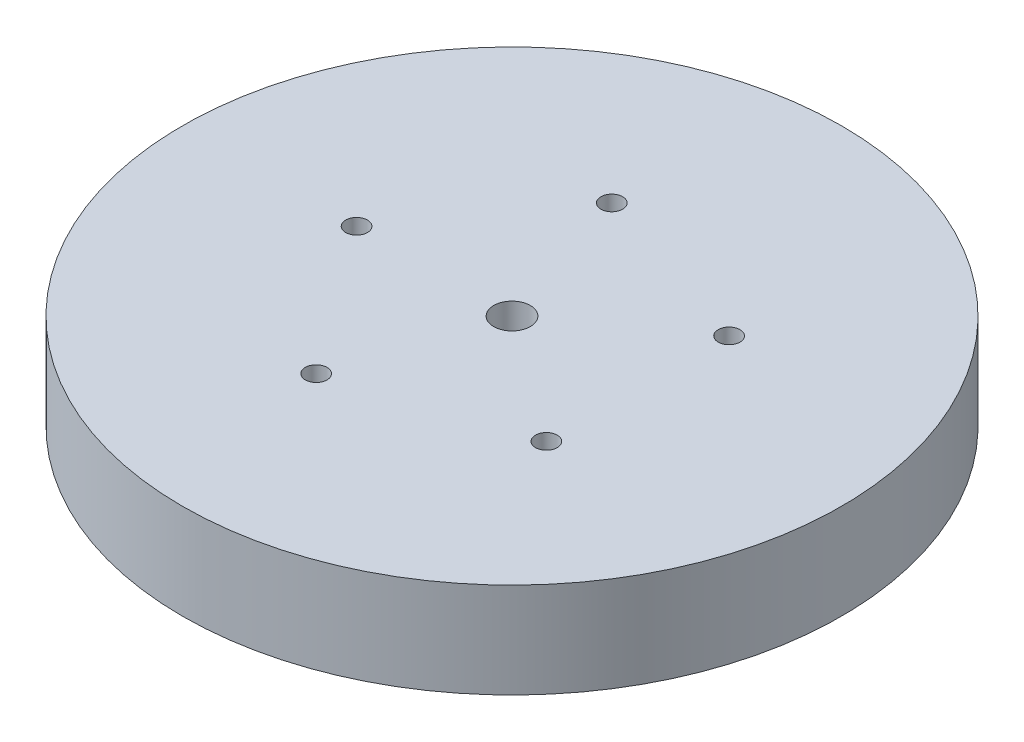
SolidWorks part; units mm, degrees
ref_plane "Front Plane" through (0, 0, 0) normal (0, 0, 1) x (1, 0, 0)
ref_plane "Top Plane" through (0, 0, 0) normal (0, 1, 0) x (1, 0, 0)
ref_plane "Right Plane" through (0, 0, 0) normal (1, 0, 0) x (0, 0, -1)
sketch "Sketch1" plane through (0, 0, 0) normal (0, 1, 0) x (1, 0, 0)
  circle A0 centre (0, 0) radius 90
  dimension "FLANGE_OD" = 180
extrude "Boss-Extrude1" add sketch "Sketch1" along normal blind 26
sketch "Sketch2" plane through (0, 0, 0) normal (0, 1, 0) x (1, 0, 0)
  circle A0 centre (0, 0) radius 5
  dimension "BORE_D" = 10
extrude "Cut-Extrude1" cut sketch "Sketch2" along normal through all
sketch "Sketch3" plane through (0, 26, 0) normal (0, 1, 0) x (1, 0, 0)
  circle A0 centre (0, 0) radius 42.4442 construction
  circle A1 centre (-42.4442, 0) radius 2.9677
  dimension "BOLT_D" = 5.9354
  dimension "BOLT_PCD" = 84.8883
extrude "Cut-Extrude2" cut sketch "Sketch3" against normal blind 21.4905
pattern_circular "CirPattern1" count 5 over 360 about axis through (0, 0, 0) along (0, 1, 0) of "Cut-Extrude2"
